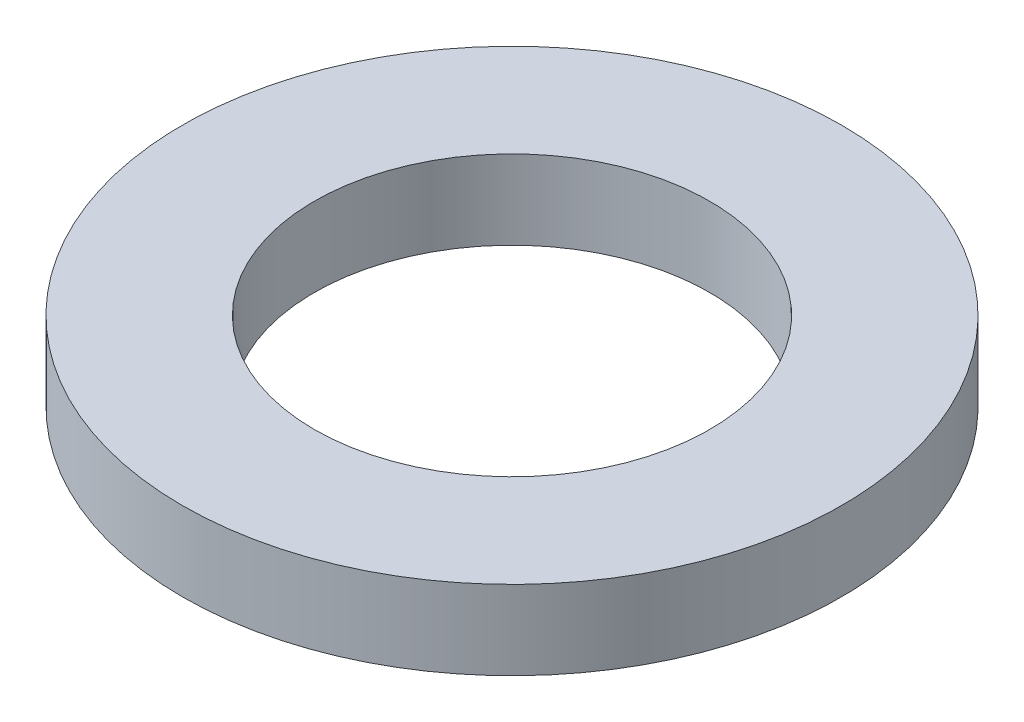
SolidWorks part; units mm, degrees
ref_plane "Front Plane" through (0, 0, 0) normal (0, 0, 1) x (1, 0, 0)
ref_plane "Top Plane" through (0, 0, 0) normal (0, 1, 0) x (1, 0, 0)
ref_plane "Right Plane" through (0, 0, 0) normal (1, 0, 0) x (0, 0, -1)
sketch "Sketch1" plane through (0, 0, 0) normal (0, 1, 0) x (1, 0, 0)
  circle A0 centre (0, 0) radius 25
  dimension "FLANGE_OD" = 50
extrude "Boss-Extrude1" add sketch "Sketch1" along normal blind 6
sketch "Sketch2" plane through (0, 0, 0) normal (0, 1, 0) x (1, 0, 0)
  circle A0 centre (0, 0) radius 15
  dimension "BORE_D" = 30
extrude "Cut-Extrude1" cut sketch "Sketch2" along normal through all
sketch "Sketch3" plane through (0, 6, 0) normal (0, 1, 0) x (1, 0, 0)
  circle A0 centre (0, 0) radius 10.615 construction
  circle A1 centre (-10.615, 0) radius 1.7398
  dimension "BOLT_D" = 3.4796
  dimension "BOLT_PCD" = 21.23
extrude "Cut-Extrude2" cut sketch "Sketch3" against normal blind 4.9344 rebuild error yes
pattern_circular "CirPattern1" count 3 over 360 rebuild error yes
